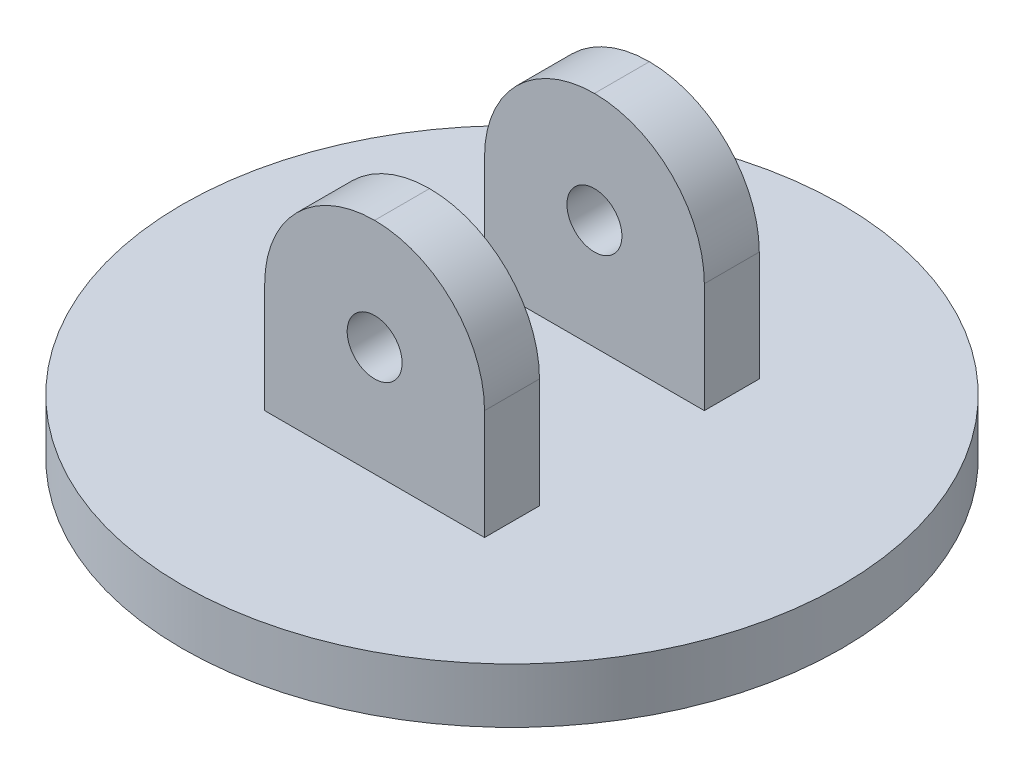
SolidWorks part; units mm, degrees
ref_plane "Ebene vorne" through (0, 0, 0) normal (0, 0, 1) x (1, 0, 0)
ref_plane "Ebene oben" through (0, 0, 0) normal (0, 1, 0) x (1, 0, 0)
ref_plane "Ebene rechts" through (0, 0, 0) normal (1, 0, 0) x (0, 0, -1)
sketch "Skizze1" plane through (0, 0, 0) normal (0, 1, 0) x (1, 0, 0)
  circle A0 centre (0, 0) radius 60
extrude "Aufsatz-Linear austragen1" add sketch "Skizze1" along normal blind 10
sketch "Skizze2" plane through (0, 10, 0) normal (0, 1, 0) x (1, 0, 0)
  line L0 (0, 0) -> (-60, 0) construction
  line L1 (-60, 0) -> (60, 0) construction
  line L2 (-35.6637, 25) -> (35.5893, 25) construction
  line L3 (-35.6637, -25) -> (35.5893, -25) construction
  line L4 (-20, -15) -> (20, -15)
  line L5 (-20, 25) -> (20, 25)
  line L6 (-20, 25) -> (-20, 15)
  line L7 (-20, 15) -> (20, 15)
  line L8 (20, 25) -> (20, 15)
  line L9 (20, -25) -> (20, -15)
  line L10 (-20, -25) -> (20, -25)
  line L11 (-20, -25) -> (-20, -15)
  circle A0 centre (0, 0) radius 60 construction
  dimension "D1" = 25
  dimension "D2" = 25
  dimension "D3" = 20
  dimension "D4" = 40
  dimension "D5" = 10
extrude "Aufsatz-Linear austragen2" add sketch "Skizze2" along normal blind 40
fillet "Verrundung1" radius 20 4 edges at (20, 50, -20) (20, 50, 20) (-20, 50, 20) (-20, 50, -20)
sketch "Skizze3" plane through (0, 0, -25) normal (0, 0, -1) x (-1, 0, 0)
  circle A0 centre (0, 30) radius 5
extrude "Schnitt-Linear austragen1" cut sketch "Skizze3" against normal through all
